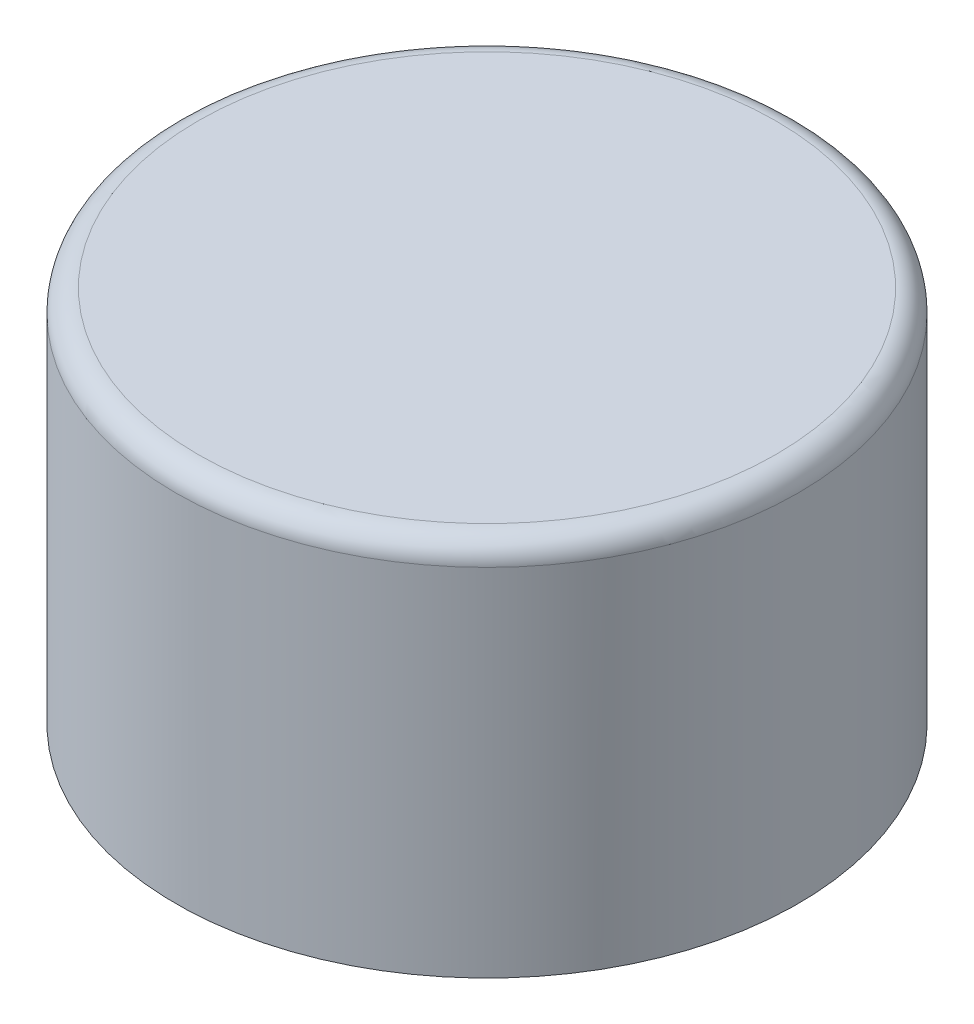
SolidWorks part; units mm, degrees
ref_plane "Front Plane" through (0, 0, 0) normal (0, 0, 1) x (1, 0, 0)
ref_plane "Top Plane" through (0, 0, 0) normal (0, 1, 0) x (1, 0, 0)
ref_plane "Right Plane" through (0, 0, 0) normal (1, 0, 0) x (0, 0, -1)
sketch "Sketch1" plane through (0, 0, 0) normal (0, 1, 0) x (1, 0, 0)
  circle A0 centre (0, 0) radius 13
  circle A1 centre (0, 0) radius 14
  dimension "D1" = 26
  dimension "D2" = 28
extrude "Boss-Extrude1" add sketch "Sketch1" along normal blind 1 contours A0 | A1 A0 region at (0, 0, 0) region at (-13.604, 0, 0)
sketch "Sketch2" plane through (0, 0, 0) normal (0, -1, 0) x (1, 0, 0)
  circle A0 centre (0, 0) radius 13
  circle A1 centre (0, 0) radius 4
  circle M2 centre (0, 0) radius 14
  dimension "D1" = 26
  dimension "D2" = 8
extrude "Boss-Extrude2" add sketch "Sketch2" along normal blind 4 contours A1 region at (0, 0, 0)
extrude "Boss-Extrude3" add sketch "Sketch2<4>" along normal blind 16 contours A0 M2 region at (-13.604, 0, 0)
sketch "Sketch2<4>" plane through (0, 0, 0) normal (0, -1, 0) x (1, 0, 0) same geometry as "Sketch2"
fillet "Fillet1" radius 4 1 edges at (0, 0, -4)
fillet "Fillet2" radius 0.5 1 edges at (0, -4, -4)
fillet "Fillet3" radius 1 2 edges at (0, 1, 14) (0, 0, -13)
